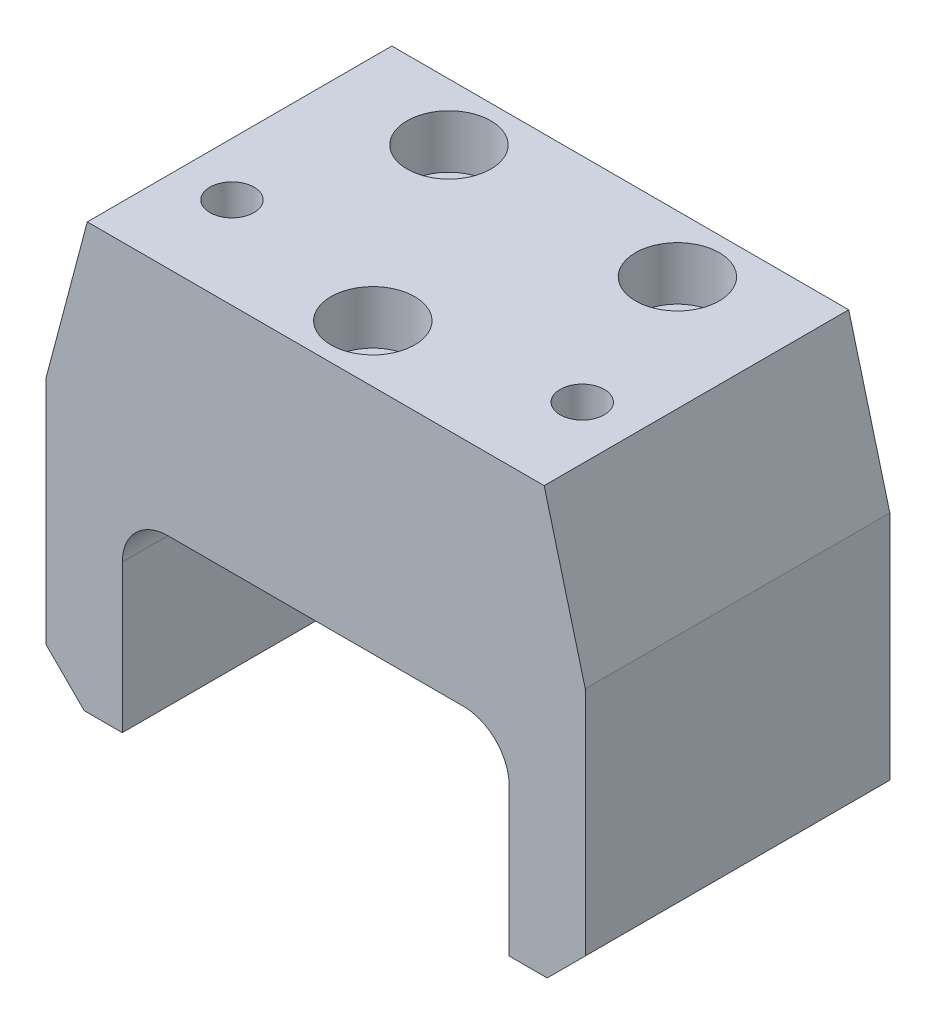
SolidWorks part; units mm, degrees
material "PET"
ref_plane "Front Plane" through (0, 0, 0) normal (0, 0, 1) x (1, 0, 0)
ref_plane "Top Plane" through (0, 0, 0) normal (0, 1, 0) x (1, 0, 0)
ref_plane "Right Plane" through (0, 0, 0) normal (1, 0, 0) x (0, 0, -1)
sketch "Sketch1" plane through (0, 0, 0) normal (0, 0, 1) x (1, 0, 0)
  line L0 (0, 19.0297) -> (0, -2.5925) construction
  line L1 (-12.9623, 0) -> (13.1829, 0) construction
  line L2 (35.4, 6) -> (-35.4, 6)
  line L3 (-35.4, 6) -> (-35.4, -49.8)
  line L4 (-35.4, -49.8) -> (-25.4, -49.8)
  line L5 (-25.4, -49.8) -> (-25.4, -24.4)
  line L6 (-25.4, -24.4) -> (25.4, -24.4)
  line L7 (35.4, -49.8) -> (25.4, -49.8)
  line L8 (25.4, -49.8) -> (25.4, -24.4)
  line L9 (35.4, 6) -> (35.4, -49.8)
  circle A0 centre (0, 0) radius 3.75 construction
  point P16 (0, -24.4)
  point P17 (0, 6)
  dimension "D1" = 7.5
  dimension "D2" = 6
  dimension "D5" = 50.8
  dimension "D6" = 24.4
  dimension "D3" = 70.8
  dimension "D4" = 25.4
extrude "Boss-Extrude1" add sketch "Sketch1" along normal mid plane 40
sketch "Sketch9" plane through (0, 0, 20) normal (0, 0, 1) x (1, 0, 0)
  line L0 (0, 0) -> (0, -24.4) construction
  line L1 (-25.4, -24.4) -> (25.4, -24.4) construction
  line L2 (-30, 6) -> (-35.4, -14.4)
  line L3 (35.4, 6) -> (-35.4, 6) construction
  line L4 (-35.4, 6) -> (-35.4, -49.8) construction
  line L5 (-35.4, -14.4) -> (-35.4, 6)
  line L6 (-35.4, 6) -> (-30, 6)
  line L7 (-25.4, -24.4) -> (-35.4, -24.4) construction
  line L8 (-35.4, -24.4) -> (-35.4, -14.4) construction
  line L9 (35.4, 6) -> (30, 6)
  line L10 (35.4, -14.4) -> (35.4, 6)
  line L11 (30, 6) -> (35.4, -14.4)
  dimension "D1" = 30
extrude "Cut-Extrude8" cut sketch "Sketch9" against normal through all
fillet "Fillet1" radius 6 2 edges at (25.4, -24.4, 0) (-25.4, -24.4, 0)
sketch "Sketch2" plane through (0, 6, 0) normal (0, 1, 0) x (1, 0, 0)
  line L0 (0, 35.9356) -> (0, 6.1551) construction
  line L1 (-23, 0.5) -> (-23, -12.5) construction
  line L2 (30, -20) -> (-30, -20) construction
  line L3 (30, 20) -> (-30, 20) construction
  circle A0 centre (0, 4) radius 2.5 construction
  circle A1 centre (0, -12.5) radius 3.05
  circle A2 centre (-23, 0.5) radius 2.9
  circle A3 centre (-23, -12.5) radius 2.9
  circle A4 centre (-15, 12.5) radius 3.05
  circle A5 centre (23, -12.5) radius 2.9
  circle A6 centre (23, 0.5) radius 2.9
  circle A7 centre (15, 12.5) radius 3.05
  dimension "D1" = 6.1
  dimension "D2" = 5.8
  dimension "D3" = 5
  dimension "D4" = 7.5
  dimension "D5" = 13
  dimension "D6" = 23
  dimension "D7" = 7.5
  dimension "D8" = 16.5
  dimension "D9" = 7.5
  dimension "D10" = 15
extrude "Cut-Extrude1" cut sketch "Sketch2" against normal blind 37
sketch "Sketch3" plane through (0, 6, 0) normal (0, 1, 0) x (1, 0, 0)
  circle A0 centre (-15, 12.5) radius 5.5
  circle A1 centre (15, 12.5) radius 5.5
  circle A2 centre (0, -12.5) radius 5.5
  dimension "D1" = 11
  dimension "D2" = 11
extrude "Cut-Extrude2" cut sketch "Sketch3" against normal blind 7
other "DeleteFace1" face at (-25.9, 6, -0.5) face at (-25.9, 6, 12.5) face at (25.9, 6, -0.5) face at (25.9, 6, 12.5) face at (25.65, -31, -0.5) face at (25.65, -31, 12.5) face at (-25.65, -31, 12.5) face at (-25.65, -31, -0.5) and patch yes
sketch "Sketch8" plane through (0, 6, 0) normal (0, 1, 0) x (1, 0, 0)
  line L0 (-23, -8) -> (0, -8) construction
  line L1 (0, -8) -> (0, 0) construction
  line L2 (30, -20) -> (-30, -20) construction
  circle A0 centre (-23, -8) radius 2.9
  circle A1 centre (23, -8) radius 2.9
  dimension "D1" = 5.8
  dimension "D2" = 46
  dimension "D3" = 12
extrude "Cut-Extrude7" cut sketch "Sketch8" against normal blind 29
chamfer "Chamfer2" distance 5 angle 45 2 edges at (-35.4, -49.8, 0) (35.4, -49.8, 0)
fillet "Fillet2" radius 2 2 edges at (25.9, -23, 8) (-25.9, -23, 8)
equation "\"M5_tap\"=4.2mm\t\t\t\t\t\t\t' Below you can do mesurements as follows: cm, mm, ft, in, m, "
equation "\"M5_clearence\"=5.5mm"
equation "\"M6_tap\"=5mm"
equation "\"M6_clearence\"=6.6mm"
equation "\"work_area_width\"=1100mm"
equation "\"work_area_depth\"=900mm"
equation "\"steel_base_width\"=3in\t"
equation "\"steel_base_height\"=2in"
equation "\"steel_base_wall_thickness\"=0.125in"
equation "\"steel_base_radius\"=6mm"
equation "\"steel_sides_width\"=3in\t\t\t\t\t'this tube is rotated so flip width/height"
equation "\"steel_sides_height\"=2in\t\t\t\t'this tube is rotated so flip width/height"
equation "\"steel_sides_wall_thickness\"=0.125in"
equation "\"steel_sides_radius\"=6mm"
equation "\"steel_gantry_width\"=4in\t\t\t\t'this tube is rotated so flip width/height"
equation "\"steel_gantry_height\"=3in\t\t\t\t'this tube is rotated so flip width/height"
equation "\"steel_gantry_wall_thickness\"=0.125in"
equation "\"steel_gantry_radius\"=6mm"
equation "\"steel_rollers_width\"=3in"
equation "\"steel_rollers_height\"=2in\t\t\t\t'keep as low as possible as this increases how big plastic parts are"
equation "\"steel_rollers_wall_thickness\"=0.125in"
equation "\"steel_rollers_radius\"=6mm"
equation "\"steel_zbox_width\"=4in\t\t\t\t\t'if the gantry height (rotated) is too thick, a wider zbox is necessary"
equation "\"steel_zbox_height\"=2in\t\t\t\t\t'hole patteren changes as the zbox and gantry height (rotated) changes."
equation "\"steel_zbox_wall_thickness\"=0.125in"
equation "\"steel_zbox_radius\"=6mm"
equation "\"alu_zangle_width\"=4in\t\t\t\t\t'check that it doesn't interfer with the gantry"
equation "\"alu_zangle_height\"=4in"
equation "\"alu_zangle_wall_thickness\"=0.375in\t\t\t'check that it doesn't interfer with the gantry"
equation "\"D3@Sketch1\"=\"steel_sides_height\" + 20"
equation "\"D5@Sketch1\"=\"steel_sides_height\""
equation "\"D6@Sketch1\"=\"steel_rollers_height\" /2 -1"
equation "\"D4@Sketch1\"=\"steel_sides_width\"/3"
